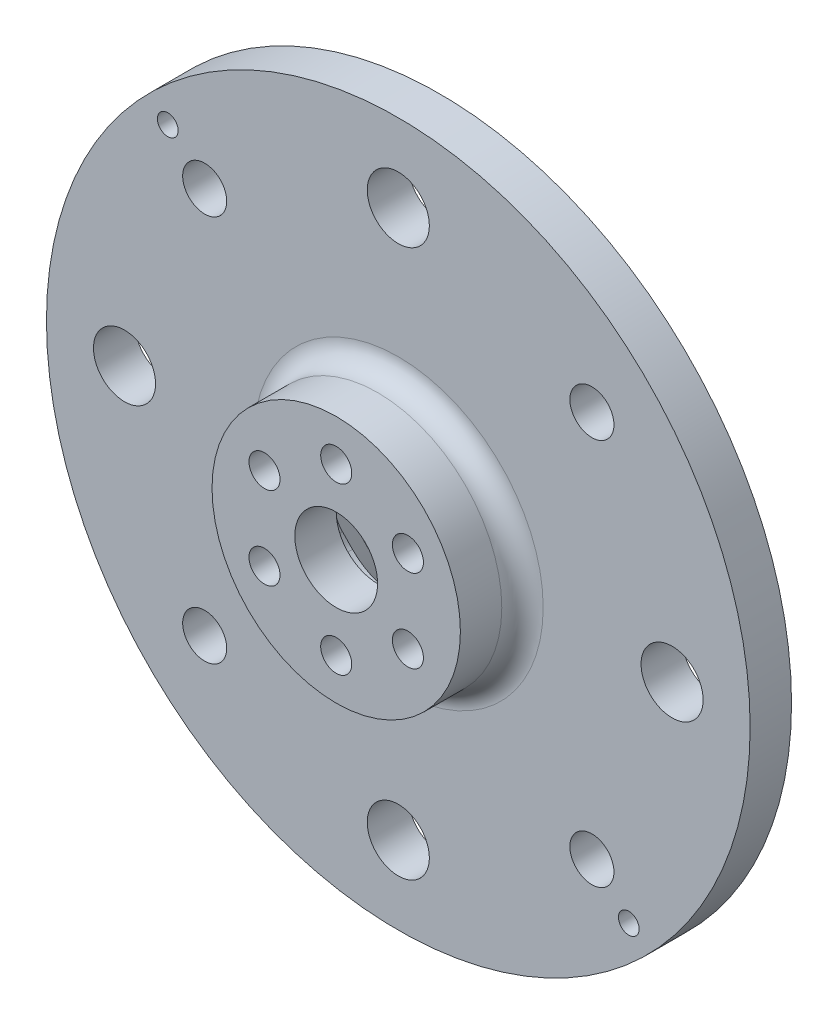
SolidWorks part; units mm, degrees
material "Plain Carbon Steel"
ref_plane "Front" through (0, 0, 0) normal (0, 0, 1) x (1, 0, 0)
ref_plane "Top" through (0, 0, 0) normal (0, 1, 0) x (1, 0, 0)
ref_plane "Right" through (0, 0, 0) normal (1, 0, 0) x (0, 0, -1)
sketch "Sketch1" plane through (0, 0, 0) normal (0, 0, 1) x (1, 0, 0)
  circle A0 centre (0, 0) radius 53.975
  circle A1 centre (0, 42) radius 4.7625
  circle A2 centre (42, 0) radius 4.7625
  circle A3 centre (0, -42) radius 4.7625
  circle A4 centre (-42, 0) radius 4.7625
  point P14 (0, 0)
  dimension "D1" = 107.95
  dimension "D2" = 9.525
  dimension "D3" = 42
  dimension "D4" = 4
extrude "Boss-Extrude1" add sketch "Sketch1" along normal blind 6.35
sketch "Sketch2" plane through (0, 0, 6.35) normal (0, 0, 1) x (1, 0, 0)
  circle A0 centre (0, 0) radius 19.05
  circle A2 centre (0, 0) radius 19.05 construction
extrude "Boss-Extrude2" add sketch "Sketch2" along normal up to surface (9.525 mm away)
sketch "Sketch3" plane through (0, 0, 0) normal (0, 0, -1) x (-1, 0, 0)
  circle A0 centre (0, 0) radius 9.8425
  dimension "D1" = 19.685
extrude "Cut-Extrude1" cut sketch "Sketch3" against normal up to surface (9.525 mm away)
sketch "Sketch4" plane through (0, 0, 9.525) normal (0, 0, -1) x (-1, 0, 0)
  circle A0 centre (0, 0) radius 6.35
  dimension "D1" = 12.7
extrude "Cut-Extrude2" cut sketch "Sketch4" against normal through all
sketch "Sketch7" plane through (0, 0, 15.875) normal (0, 0, 1) x (1, 0, 0)
  circle A0 centre (0, 12.7) radius 2.3813
  circle A1 centre (0, 12.7) radius 2.3813 construction
  circle A2 centre (10.9985, 6.35) radius 2.3813
  circle A3 centre (10.9985, -6.35) radius 2.3813
  circle A4 centre (0, -12.7) radius 2.3813
  circle A5 centre (-10.9985, -6.35) radius 2.3813
  circle A6 centre (-10.9985, 6.35) radius 2.3813
  circle A7 centre (0, 0) radius 6.35 construction
  point P17 (0, 0)
  dimension "D1" = 6
fillet "Fillet2" radius 3.175 1 edges at (19.05, 0, 6.35)
chamfer "Chamfer1" distance 6.35 angle 45 1 edges at (-9.8425, 0, 0)
extrude "Boss-Extrude4" add sketch "Sketch10" along normal up to surface (3.175 mm away) up to face at (16.1925, 0, 0)
sketch "Sketch10" plane through (0, 0, 9.525) normal (0, 0, -1) x (-1, 0, 0)
  line L1 (7.9375, -5.8199) -> (-7.9375, -5.8199) construction
  line L2 (7.9375, -5.8199) -> (7.9375, 5.8199)
  line L3 (7.9375, 5.8199) -> (-7.9375, 5.8199) construction
  line L4 (-7.9375, -5.8199) -> (-7.9375, 5.8199)
  line L5 (7.9375, -5.8199) -> (-7.9375, 5.8199) construction
  line L6 (7.9375, 5.8199) -> (-7.9375, -5.8199) construction
  circle A0 centre (0, 0) radius 9.8425 construction
  arc A1 (-7.9375, 5.8199) -> (-7.9375, -5.8199) centre (0, 0) ccw
  arc A2 (7.9375, -5.8199) -> (7.9375, 5.8199) centre (0, 0) ccw
  point P0 (0, 0)
  dimension "D1" = 15.875
extrude "Cut-Extrude4" cut sketch "Sketch7" against normal blind 6.35
hole_wizard "1/4 Clearance Hole1" positions "Sketch8" profile "Sketch9" hole size "1/4" standard "ANSI Inch" end condition through all
sketch "Sketch8" plane through (0, 0, 6.35) normal (0, 0, 1) x (1, 0, 0)
  point P0 (-29.6985, -29.6985)
  point P2 (29.6985, -29.6985)
  point P4 (29.6985, 29.6985)
  point P6 (-29.6985, 29.6985)
sketch "Sketch9" plane through (-29.6985, -29.6985, 6.35) normal (1, 0, 0) x (0, -1, 0)
  line L0 (0, 0) -> (0, 6.35)
  line L1 (0, 6.35) -> (3.3782, 6.35)
  line L2 (3.3782, 6.35) -> (3.3782, 0)
  line L5 (3.3782, 0) -> (0, 0)
  line L11 (0, -6.35) -> (0, 107.95) construction
  dimension "Thru Hole Dia." = 6.7564
  dimension "Thru Hole Depth" = 6.35
fillet "Fillet3" radius 3.175 4 edges at (-7.9375, 5.8199, 7.9375) (-7.9375, -5.8199, 7.9375) (7.9375, -5.8199, 7.9375) (7.9375, 5.8199, 7.9375)
hole_wizard "1/8 (0.1250) Dowel Hole1" positions "Sketch11" profile "Sketch12" hole size "1/8" standard "ANSI Inch"
sketch "Sketch11" plane through (0, 0, 0) normal (0, 0, -1) x (-1, 0, 0)
  point P3 (-35.3598, -35.3598)
  point P9 (35.3598, 35.3598)
sketch "Sketch12" plane through (35.3598, -35.3598, 0) normal (1, 0, 0) x (0, 1, 0)
  line L0 (0, 0) -> (0, 7.3029)
  line L1 (0, 7.3029) -> (1.5875, 6.349)
  line L2 (1.5875, 6.349) -> (1.5875, 0)
  line L5 (1.5875, 0) -> (0, 0)
  line L10 (0, 7.3029) -> (-1.5875, 6.349) construction
  line L11 (0, -6.35) -> (0, 107.95) construction
  dimension "Hole Dia." = 3.175
  dimension "Hole Depth" = 6.349
  dimension "Drill Angle" = 118
equation "\"D3@Sketch1\"=42mm"
